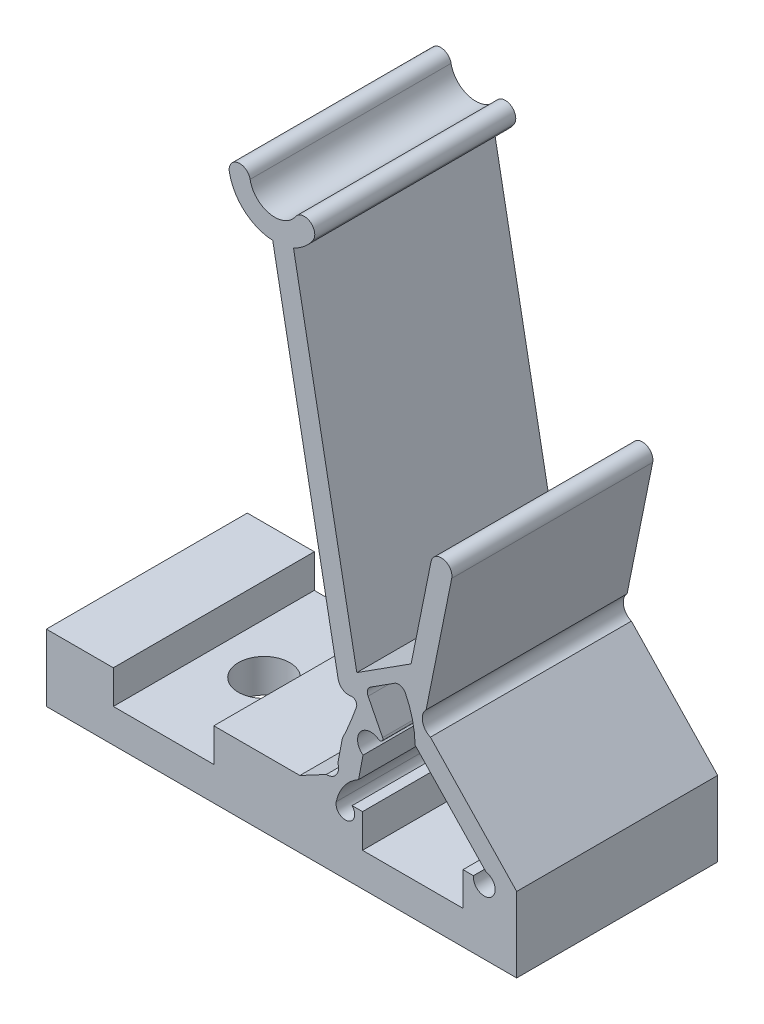
SolidWorks part; units mm, degrees
ref_plane "Front Plane" through (0, 0, 0) normal (0, 0, 1) x (1, 0, 0)
ref_plane "Top Plane" through (0, 0, 0) normal (0, 1, 0) x (1, 0, 0)
ref_plane "Right Plane" through (0, 0, 0) normal (1, 0, 0) x (0, 0, -1)
sketch "Sketch-SkeletonConfigUp" plane through (0, 0, 0) normal (0, 0, 1) x (1, 0, 0)
  line L0 (0, 0) -> (0, -50000) construction
  line L1 (0, 0) -> (7.455, 0.2734) construction
  line L2 (9.9233, 0.3639) -> (10.6101, 4.558) construction
  line L3 (10.6101, 4.558) -> (7.9471, 2.8569) construction
  line L4 (7.9471, 2.8569) -> (7.455, 0.2734) construction
  line L5 (10.6101, 4.558) -> (12.0093, 11.478) construction
  line L6 (7.9471, 2.8569) -> (4.1146, 23.199) construction
  line L7 (7.455, 0.2734) -> (9.9233, 0.3639) construction
  line L8 (-989.4051, -36.2798) -> (9.9233, 0.3639) construction
  dimension "D2" = 7.46
  dimension "D3" = 2.47
  dimension "D4" = 4.25
  dimension "D5" = 78.6
  dimension "D6" = 3.16
  dimension "D7" = 7.06
  dimension "D8" = 20.7
  dimension "D9" = 2.63
  dimension "D10" = 46
  dimension "D11" = 111.9
  dimension "D12" = 92.1
sketch "Sketch-SkeletonConfigDown" plane through (0, 0, 0) normal (0, 0, 1) x (1, 0, 0)
  line L0 (0, 0) -> (0, -50000) construction
  line L1 (0, 0) -> (7.455, 0.2734) construction
  line L2 (9.9233, 0.3639) -> (10.6101, 4.558) construction
  line L3 (10.6101, 4.558) -> (9.7761, 1.5101) construction
  line L4 (9.7761, 1.5101) -> (7.455, 0.2734) construction
  line L5 (10.6101, 4.558) -> (7.0062, 10.6288) construction
  line L6 (9.7761, 1.5101) -> (-6.7111, 14.0265) construction
  line L7 (7.455, 0.2734) -> (9.9233, 0.3639) construction
  line L8 (-993.745, -36.439) -> (9.9233, 0.3639) construction
  dimension "D2" = 7.46
  dimension "D3" = 2.47
  dimension "D4" = 4.25
  dimension "D5" = 78.6
  dimension "D6" = 3.16
  dimension "D7" = 7.06
  dimension "D8" = 20.7
  dimension "D9" = 2.63
  dimension "D10" = 46
  dimension "D11" = 111.9
  dimension "D1" = 92.1
sketch "Sketch-ConfigDown" plane through (0, 0, 0) normal (0, 0, 1) x (1, 0, 0)
  line L3 (7.2122, -0.2359) -> (5.3047, -0.3058) construction
  line L4 (9.7761, 1.5101) -> (-6.7111, 14.0265) construction
  line L6 (-200859.4238, -7365.1807) -> (9.9233, 0.3639) construction
  line L7 (7.2122, -0.2359) -> (15.5786, 0.0709) construction
  line L9 (7.455, 0.2734) -> (9.9233, 0.3639) construction
  line L10 (10.9008, 0.9001) -> (10.9374, -0.0993) construction
  line L15 (9.3493, 0.7161) -> (8.352, 0.1848)
  line L18 (8.512, 1.4031) -> (8.9823, 0.5206) construction
  line L19 (6.5762, 10.3736) -> (9.0074, 6.2784)
  line L20 (-5.3148, 12.3387) -> (8.4132, 1.917)
  line L21 (8.2015, 3.3332) -> (-4.7101, 13.1352)
  line L22 (9.7761, 1.5101) -> (7.455, 0.2734) construction
  line L23 (2.9291, 6.0802) -> (3.5338, 6.8767) construction
  line L26 (10.6101, 4.558) -> (14.4503, 0.5299) construction
  line L27 (10.2553, 5.1557) -> (9.3507, 1.85) construction
  line L28 (11.0112, 4.862) -> (15.5786, 0.0709) construction
  line L29 (14.5562, -0.3058) -> (10.7658, 3.6702) construction
  line L30 (12.9938, 1.3331) -> (13.7176, 2.0231) construction
  line L34 (5.3047, -0.3058) -> (5.3047, -3.4808) construction
  line L36 (5.3047, -3.4808) -> (15.5786, -3.4808)
  line L37 (15.5786, -3.4808) -> (15.5786, 0.0709)
  line L38 (-8.0357, 12.2817) -> (-6.0162, 14.9419) construction
  line L39 (10.6101, 4.558) -> (9.7761, 1.5101) construction
  line L40 (9.7556, 3.3297) -> (10.7202, 3.0657) construction
  line L42 (7.4361, 10.8841) -> (10.4021, 5.8879)
  line L43 (8.1032, 7.8014) -> (8.9631, 8.3119) construction
  line L44 (10.6101, 4.558) -> (7.0062, 10.6288) construction
  line L45 (7.7789, -0.3058) -> (5.3047, -0.3058) construction
  line L46 (14.5562, -0.3058) -> (15.5786, -0.3058) construction
  line L47 (13.528, -0.3058) -> (7.7789, -0.3058)
  line L48 (9.0074, 6.2784) -> (8.2015, 3.3332)
  line L49 (15.5786, 0.0709) -> (15.28, 0.3842)
  line L50 (10.7658, 3.6702) -> (9.7307, 4.7558) construction
  line L51 (15.28, 0.3842) -> (14.5562, -0.3058) construction
  line L52 (14.5815, 0.7545) -> (14.7625, 0.927) construction
  line L53 (13.5212, 0.7799) -> (14.2449, 1.4699) construction
  line L54 (11.0112, 4.862) -> (10.4545, 5.4459) construction
  line L55 (10.7911, 4.7305) -> (10.972, 4.903) construction
  line L56 (9.7307, 4.7558) -> (10.4545, 5.4459) construction
  line L57 (10.7658, 3.6702) -> (11.4896, 4.3602) construction
  line L58 (10.7911, 4.7305) -> (10.4292, 4.3855) construction
  line L59 (11.4896, 4.3602) -> (14.2449, 1.4699)
  line L60 (13.5212, 0.7799) -> (10.7658, 3.6702)
  line L61 (10.4545, 5.4459) -> (10.4021, 5.8879)
  line L62 (7.3374, 0.494) -> (7.2199, 0.7146) construction
  line L63 (7.0282, -0.5206) -> (6.3041, -0.9064) construction
  line L64 (7.8818, 1.0673) -> (8.352, 0.1848) construction
  line L65 (6.558, 0.362) -> (7.0282, -0.5206) construction
  line L66 (6.558, 0.362) -> (5.3047, -0.3058)
  line L67 (6.558, 0.362) -> (7.8818, 1.0673) construction
  line L68 (7.3374, 0.494) -> (7.5725, 0.0527) construction
  line L69 (10.2029, 2.304) -> (10.8079, 2.6264) construction
  line L70 (10.6731, 1.4215) -> (11.1125, 1.6556) construction
  line L71 (9.6585, 1.7307) -> (9.541, 1.9513) construction
  line L72 (8.8791, 1.5987) -> (9.3493, 0.7161) construction
  line L73 (10.2029, 2.304) -> (10.6731, 1.4215) construction
  line L74 (9.6585, 1.7307) -> (9.8936, 1.2894) construction
  line L75 (7.8818, 1.0673) -> (8.8791, 1.5987)
  line L76 (8.4132, 1.917) -> (9.4143, 2.4504)
  line L77 (9.6228, 4.1445) -> (11.1323, 2.561)
  line L78 (11.1323, 2.561) -> (11.3028, 2.3822)
  line L79 (-6.7111, 14.0265) -> (-5.0362, 14.2558) construction
  line L80 (-6.7111, 14.0265) -> (-6.7111, -3.4808) construction
  line L81 (5.3047, -3.4808) -> (-6.7111, -3.4808)
  line L82 (-6.7111, -3.4808) -> (-6.7111, -0.3058)
  line L83 (-6.7111, -0.3058) -> (5.3047, -0.3058)
  line L84 (8.8791, 1.5987) -> (10.2029, 2.304) construction
  arc A2 (-7.4311, 13.0782) -> (-5.5316, 14.188) centre (-6.7111, 14.0265) ccw
  arc A3 (-4.7101, 13.1352) -> (-4.5408, 14.3236) centre (-6.7111, 14.0265) ccw
  arc A4 (-8.0357, 12.2817) -> (-7.4311, 13.0782) centre (-7.7334, 12.68) cw
  arc A5 (-4.5408, 14.3236) -> (-5.5316, 14.188) centre (-5.0362, 14.2558) ccw
  arc A6 (-8.0357, 12.2817) -> (-5.3148, 12.3387) centre (-6.7111, 14.0265) ccw
  arc A7 (6.5762, 10.3736) -> (7.4361, 10.8841) centre (7.0062, 10.6288) cw
  arc A8 (15.28, 0.3842) -> (14.2449, 1.4699) centre (15.4863, 1.6171) cw
  arc A9 (14.5562, -0.3058) -> (13.5212, 0.7799) centre (13.3149, -0.453) ccw
  arc A10 (10.4545, 5.4459) -> (11.4896, 4.3602) centre (11.6958, 5.593) ccw
  arc A11 (9.7307, 4.7558) -> (10.7658, 3.6702) centre (9.5245, 3.523) cw
  arc A12 (7.8818, 1.0673) -> (6.558, 0.362) centre (6.7496, 1.5972) cw
  arc A13 (7.0282, -0.5206) -> (8.352, 0.1848) centre (8.1603, -1.0505) cw
  arc A14 (7.0282, -0.5206) -> (7.7789, -0.3058) centre (7.4971, -0.74) ccw
  arc A15 (8.8791, 1.5987) -> (10.2029, 2.304) centre (9.0707, 2.8339) ccw
  arc A16 (9.3493, 0.7161) -> (10.6731, 1.4215) centre (10.4814, 0.1863) cw
  arc A19 (10.2029, 2.304) -> (9.4143, 2.4504) centre (9.8276, 2.4796) ccw
  arc A20 (14.5562, -0.3058) -> (13.528, -0.3058) centre (14.0421, -0.3668) cw
  arc A21 (9.7307, 4.7558) -> (9.6228, 4.1445) centre (9.6795, 4.4497) ccw
  arc A22 (10.6731, 1.4215) -> (11.3028, 2.3822) centre (10.7698, 2.0448) ccw
  point P24 (8.7471, 0.9618)
  point P28 (10.9191, 0.4004)
  point P30 (8.5332, 8.0566)
  point P43 (10.2379, 3.1977)
  point P47 (14.5815, 0.7545)
  point P51 (3.2315, 6.4785)
  point P61 (13.3557, 1.6781)
  dimension "D3" = 2.3812
  dimension "D4" = 4.3812
  dimension "D1" = 1
  dimension "D8" = 1.5
  dimension "D12" = 1.5
  dimension "D6" = 7
  dimension "D2" = 3.175
  dimension "D7" = 1.5
  dimension "D9" = 1.5
  dimension "D10" = 0.25
  dimension "D11" = 1.5
  dimension "D13" = 0.5
  dimension "D14" = 0.5
  dimension "D15" = 45
sketch "Sketch-ConfigUp" plane through (0, 0, 0) normal (0, 0, 1) x (1, 0, 0)
  line L1 (7.3156, 2.2137) -> (7.1042, 1.1037)
  line L2 (8.0635, 0.796) -> (13.3219, 0.9888) construction
  line L3 (10.1988, -0.1264) -> (6.8464, -0.2493) construction
  line L4 (7.9471, 2.8569) -> (7.455, 0.2734) construction
  line L5 (11.5192, 11.5771) -> (10.5754, 6.909)
  line L6 (7.455, 0.2734) -> (9.9233, 0.3639) construction
  line L7 (10.1988, -0.1264) -> (15.5786, 0.0709) construction
  line L9 (10.6101, 4.558) -> (7.9471, 2.8569) construction
  line L10 (8.9451, 0.8283) -> (8.9817, -0.171) construction
  line L11 (7.2099, 1.6587) -> (8.1922, 1.4716) construction
  line L12 (8.7452, 3.96) -> (9.2835, 3.1173) construction
  line L15 (9.9233, 0.3639) -> (10.6101, 4.558) construction
  line L16 (9.7754, 2.5547) -> (10.7623, 2.3931) construction
  line L17 (12.4994, 11.3789) -> (11.2863, 5.379)
  line L18 (10.6101, 4.558) -> (12.0093, 11.478) construction
  line L19 (10.5058, 6.5648) -> (11.486, 6.3666) construction
  line L20 (4.0182, 21.0106) -> (7.1163, 4.5661)
  line L21 (8.0021, 5.2653) -> (5.0009, 21.1957)
  line L22 (7.9471, 2.8569) -> (4.1146, 23.199) construction
  line L23 (6.0985, 9.9681) -> (7.0813, 10.1533) construction
  line L24 (8.3015, 3.6766) -> (10.1621, 4.8651) construction
  line L26 (10.6101, 4.558) -> (14.4503, 0.5299) construction
  line L27 (-200855.0838, -7365.0216) -> (9.9233, 0.3639) construction
  line L30 (10.7658, 3.6702) -> (11.4896, 4.3602) construction
  line L34 (6.8464, -0.2493) -> (6.8464, -3.4808) construction
  line L38 (1.9619, 22.7935) -> (4.1146, 23.199) construction
  line L39 (4.1146, 23.199) -> (5.9236, 21.9636) construction
  line L40 (13.528, -0.3058) -> (7.7789, -0.3058) construction
  line L41 (13.528, -0.3058) -> (7.7789, -0.3058)
  line L42 (11.2489, 5.194) -> (10.7354, 2.6543) construction
  line L43 (10.1621, 4.8651) -> (9.715, 2.6538) construction
  line L44 (6.8464, -0.2493) -> (5.1916, -0.31) construction
  line L45 (8.0635, 0.796) -> (8.0865, 0.9166) construction
  line L46 (8.0635, 0.796) -> (7.8058, -0.5569) construction
  line L47 (7.2094, 0.3201) -> (6.9638, 0.3669) construction
  line L48 (7.2094, 0.3201) -> (7.7006, 0.2266) construction
  line L49 (6.8235, -0.3698) -> (7.8058, -0.5569) construction
  line L50 (7.4382, 2.8574) -> (7.5963, 3.6872) construction
  line L51 (8.3979, 2.5516) -> (8.5786, 3.5001) construction
  line L52 (7.3156, 2.2137) -> (8.2979, 2.0266) construction
  line L53 (7.5963, 3.6872) -> (8.5786, 3.5001) construction
  line L54 (7.7015, 2.9037) -> (8.1927, 2.8101) construction
  line L55 (7.7015, 2.9037) -> (7.4559, 2.9505) construction
  line L56 (8.1564, 2.8991) -> (7.6708, 3.0185) construction
  line L57 (7.1163, 4.5661) -> (7.4382, 2.8574) construction
  line L58 (11.2863, 5.379) -> (10.3061, 5.5772) construction
  line L59 (7.4382, 2.8574) -> (7.3156, 2.2137) construction
  line L60 (7.8068, 2.1202) -> (8.6839, 3.337) construction
  line L61 (8.2979, 2.0266) -> (8.0865, 0.9166)
  line L62 (7.1042, 1.1037) -> (8.0865, 0.9166) construction
  line L69 (10.8552, 4.5085) -> (11.1002, 4.4589) construction
  line L70 (7.7789, -0.3058) -> (5.3047, -0.3058) construction
  line L71 (7.7789, -0.3058) -> (5.3047, -0.3058) construction
  line L73 (7.1042, 1.1037) -> (6.8464, -0.2493) construction
  line L74 (10.2687, 5.3922) -> (11.2489, 5.194) construction
  line L75 (9.9714, 3.922) -> (10.9516, 3.7238) construction
  line L76 (10.8552, 4.5085) -> (10.3651, 4.6076) construction
  line L77 (8.3979, 2.5516) -> (8.2979, 2.0266) construction
  line L78 (9.5833, 3.3088) -> (8.3979, 2.5516) construction
  line L79 (8.0021, 5.2653) -> (10.5754, 6.909)
  line L80 (8.0021, 5.2653) -> (8.3015, 3.6766) construction
  line L81 (10.5058, 6.5648) -> (10.1621, 4.8651) construction
  line L82 (10.5058, 6.5648) -> (10.5754, 6.909) construction
  line L83 (11.4896, 4.3602) -> (10.7658, 3.6702) construction
  line L84 (11.1158, 4.8153) -> (10.6255, 4.7174) construction
  line L106 (6.558, 0.362) -> (5.3047, -0.3058)
  line L107 (5.3047, -0.3058) -> (-6.7111, -0.3058)
  line L108 (-6.7111, -0.3058) -> (-6.7111, -3.4808)
  line L109 (-6.7111, -3.4808) -> (15.5786, -3.4808)
  line L110 (15.5786, -3.4808) -> (15.5786, 0.0709)
  line L112 (15.5786, 0.0709) -> (11.4896, 4.3602)
  line L114 (11.1277, 4.0152) -> (10.7962, 5.4781) construction
  line L115 (9.5833, 3.3088) -> (10.5323, 3.915) construction
  line L116 (13.3219, 0.9888) -> (10.7658, 3.6702)
  line L117 (10.7658, 3.6702) -> (10.5323, 3.915) construction
  line L118 (10.6101, 4.558) -> (7.9471, 2.8569) construction
  line L119 (8.6839, 3.337) -> (9.4161, 2.8092) construction
  line L120 (8.6839, 3.337) -> (7.8068, 3.9692) construction
  line L121 (9.0288, 3.0406) -> (8.2979, 2.0266) construction
  line L123 (9.7888, 5.7212) -> (8.6571, 4.9983)
  line L124 (8.5388, 4.5661) -> (9.2253, 3.2085)
  line L126 (13.3219, 0.9888) -> (14.1275, 0.1438)
  line L127 (11.2489, 5.194) -> (11.2863, 5.379) construction
  arc A0 (11.5192, 11.5771) -> (12.4994, 11.3789) centre (12.0093, 11.478) cw
  arc A2 (2.9446, 22.9786) -> (5.0978, 22.5276) centre (4.1146, 23.199) ccw
  arc A3 (5.0009, 21.1957) -> (5.9236, 21.9636) centre (4.1146, 23.199) ccw
  arc A4 (1.9619, 22.7935) -> (2.9446, 22.9786) centre (2.4533, 22.886) cw
  arc A5 (5.9236, 21.9636) -> (5.0978, 22.5276) centre (5.5107, 22.2456) ccw
  arc A6 (1.9619, 22.7935) -> (4.0182, 21.0106) centre (4.1146, 23.199) ccw
  arc A7 (13.528, -0.3058) -> (14.5562, -0.3058) centre (14.0421, -0.3668) ccw construction
  arc A8 (13.528, -0.3058) -> (14.1275, 0.1438) centre (14.0421, -0.3668) ccw
  arc A9 (7.1042, 1.1037) -> (6.8235, -0.3698) centre (5.9815, 0.554) cw construction
  arc A10 (7.8058, -0.5569) -> (8.0865, 0.9166) centre (8.9285, -0.0073) cw construction
  arc A11 (7.3156, 2.2137) -> (7.5963, 3.6872) centre (6.4736, 3.1376) ccw construction
  arc A12 (8.2979, 2.0266) -> (8.5786, 3.5001) centre (9.4206, 2.5762) cw construction
  arc A13 (11.2489, 5.194) -> (10.9516, 3.7238) centre (12.0804, 4.2607) ccw construction
  arc A14 (10.2687, 5.3922) -> (9.9714, 3.922) centre (9.1399, 4.8553) cw construction
  arc A15 (8.0865, 0.9166) -> (7.0282, -0.5206) centre (9.1391, -0.9668) ccw
  arc A16 (7.1042, 1.1037) -> (6.558, 0.362) centre (6.5823, 0.916) cw
  arc A17 (7.0282, -0.5206) -> (7.7789, -0.3058) centre (7.4604, -0.612) ccw
  arc A18 (11.4896, 4.3602) -> (11.2863, 5.379) centre (11.7287, 4.9376) cw
  arc A19 (8.2979, 2.0266) -> (9.0288, 3.0406) centre (8.6634, 2.5336) cw
  arc A21 (7.3156, 2.2137) -> (7.9864, 3.8397) centre (-8.9784, 9.887) ccw
  arc A22 (7.9864, 3.8397) -> (7.7104, 4.1617) centre (7.7563, 3.9218) ccw
  arc A23 (10.7658, 3.6702) -> (10.3061, 5.5772) centre (6.3229, 3.6081) ccw
  arc A24 (7.7104, 4.1617) -> (7.1163, 4.5661) centre (7.615, 4.66) cw
  arc A25 (9.0288, 3.0406) -> (9.2253, 3.2085) centre (9.1066, 3.1485) ccw
  arc A27 (10.3061, 5.5772) -> (9.7888, 5.7212) centre (9.9829, 5.4174) ccw
  arc A39 (8.6571, 4.9983) -> (8.5388, 4.5661) centre (8.8369, 4.7168) ccw
  point P25 (9.0144, 3.5387)
  point P27 (7.701, 1.5651)
  point P28 (8.9634, 0.3287)
  point P36 (10.2689, 2.4739)
  point P38 (10.9959, 6.4657)
  point P51 (6.5899, 10.0607)
  point P61 (11.1277, 4.0152)
  dimension "D3" = 2.3812
  dimension "D4" = 4.3812
  dimension "D13" = 0.625
  dimension "D17" = 0.625
  dimension "D1" = 1
  dimension "D5" = 7
  dimension "D10" = 1.5
  dimension "D11" = 0.25
  dimension "D8" = 1.5
  dimension "D9" = 0.25
  dimension "D6" = 1.5
  dimension "D7" = 0.25
  dimension "D12" = 1.5
  dimension "D15" = 0.5
  dimension "D16" = 1.5
  dimension "D18" = 0.5
  dimension "D19" = 25
  dimension "D20" = 1.5
  dimension "D14" = 45
extrude "Boss-ConfigUp" add sketch "Sketch-ConfigUp" along normal blind 9.525
sketch "Sketch2" plane through (0.0043, -0.3058, 0) normal (0, -1, 0) x (-1, 0, 0)
  line L1 (-13.0304, 0) -> (-8.2679, 0)
  line L2 (-13.0304, 0) -> (-13.0304, -9.525)
  line L3 (-13.0304, -9.525) -> (-8.2679, -9.525)
  line L4 (-8.2679, 0) -> (-8.2679, -9.525)
  line L5 (-13.5237, 0) -> (-13.0304, 0) construction
  line L7 (-8.2679, 0) -> (-7.7746, 0) construction
  line L10 (-15.5743, -4.7625) -> (6.7155, -4.7625) construction
  line L12 (-13.0304, 0) -> (-8.2679, -9.525) construction
  line L17 (-13.0304, -9.525) -> (-8.2679, 0) construction
  line L18 (6.7155, 0) -> (-15.5743, 0) construction
  line L19 (6.7155, -9.525) -> (6.7155, 0) construction
  line L20 (3.5405, -9.525) -> (3.5405, 0)
  line L21 (3.5405, -9.525) -> (-1.222, -9.525)
  line L22 (3.5405, 0) -> (-1.222, 0)
  line L23 (-1.222, -9.525) -> (-1.222, 0)
  line L24 (3.5405, -9.525) -> (-1.222, 0) construction
  line L25 (3.5405, 0) -> (-1.222, -9.525) construction
  line L26 (6.7155, -9.525) -> (-15.5743, -9.525) construction
  line L27 (-15.5743, -9.525) -> (-15.5743, 0) construction
  point P4 (-10.6492, -4.7625)
  point P26 (1.1592, -4.7625)
  dimension "D1" = 4.7625
  dimension "D2" = 3.175
extrude "Cut-NutSlot" cut sketch "Sketch2" along normal blind 1.5875
hole_wizard "#2 Clearance Hole1" positions "Sketch4" profile "Sketch3" hole size "#2" standard "ANSI Inch" end condition up to next
sketch "Sketch4" plane through (0, -3.4808, 0) normal (0, -1, 0) x (-1, 0, 0)
  line L16 (-13.0347, 0) -> (-8.2722, -9.525) construction
  point P40 (-10.6535, -4.7625)
  point P44 (1.1549, -4.7625)
sketch "Sketch3" plane through (10.6535, -3.4808, 4.7625) normal (1, 0, 0) x (0, 0, -1)
  line L0 (0, 0) -> (0, 1.5875)
  line L1 (0, 1.5875) -> (1.2192, 1.5875)
  line L2 (1.2192, 1.5875) -> (1.2192, 0)
  line L5 (1.2192, 0) -> (0, 0)
  line L11 (0, -6.35) -> (0, 107.95) construction
  dimension "Thru Hole Dia." = 2.4384
  dimension "Thru Hole Depth" = 1.5875
ref_plane "Plane-Midplane" through (0, 0, 4.7625) normal (0, 0, -1) x (-1, 0, 0)
equation "\"axle-diameter\"=2"
equation "\"switch-thickness\"=12"
equation "\"base-width\"=4.0"
equation "\"axle-bushing-radius\"=3"
equation "\"clearance\"= 0.25"
equation "\"arm-width\"=1.0"
equation "\"min-diameter\"=70"
equation "\"alpha\"=92.1"
equation "\"beta\"=26.0"
equation "\"gamma\"=78.6"
equation "\"delta\"=111.9"
equation "\"epsilon\"=46.0"
equation "\"eta\"=-228.1"
equation "\"l_AB\"=2.47"
equation "\"l_AC\"=2.63"
equation "\"l_BD\"=4.25"
equation "\"l_CD\"=3.16"
equation "\"l_CE\"=20.70"
equation "\"l_DF\"=7.06"
equation "\"l_OA\"=7.46"
equation "\"D2@Sketch-SkeletonConfigUp\" = \"l_OA\""
equation "\"D3@Sketch-SkeletonConfigUp\" = \"l_AB\""
equation "\"D4@Sketch-SkeletonConfigUp\" = \"l_BD\""
equation "\"D5@Sketch-SkeletonConfigUp\" = \"gamma\""
equation "\"D6@Sketch-SkeletonConfigUp\" = \"l_CD\""
equation "\"D7@Sketch-SkeletonConfigUp\" = \"l_DF\""
equation "\"D8@Sketch-SkeletonConfigUp\" = \"l_CE\""
equation "\"D9@Sketch-SkeletonConfigUp\" = \"l_AC\""
equation "\"D_groove\"=2.3812"
equation "\"D3@Sketch-ConfigUp\" = \"D_groove\""
equation "\"D4@Sketch-ConfigUp\" = \"D_groove\" + 2 * \"arm-width\""
equation "\"D7@Sketch-SkeletonConfigDown\" = \"l_DF\""
equation "\"D6@Sketch-SkeletonConfigDown\" = \"l_CD\""
equation "\"D2@Sketch-SkeletonConfigDown\" = \"l_OA\""
equation "\"D3@Sketch-SkeletonConfigDown\" = \"l_AB\""
equation "\"D9@Sketch-SkeletonConfigDown\" = \"l_AC\""
equation "\"D8@Sketch-SkeletonConfigDown\" = \"l_CE\""
equation "\"D5@Sketch-SkeletonConfigDown\" = \"gamma\""
equation "\"D4@Sketch-SkeletonConfigDown\" = \"l_BD\""
equation "\"D1@Sketch-SkeletonConfigDown\" = \"alpha\""
equation "\"D5@Sketch-ConfigDown\" = \"arm-width\""
equation "\"hinge_length\"=1.5"
equation "\"hinge_depth\"=0.25"
equation "\"D9@Sketch-ConfigDown\" = \"hinge_length\""
equation "\"D10@Sketch-ConfigDown\" = \"hinge_depth\""
equation "\"D8@Sketch-ConfigDown\" = \"hinge_length\""
equation "\"D11@Sketch-ConfigDown\" = \"hinge_length\""
equation "\"D12@Sketch-ConfigDown\" = \"hinge_length\""
equation "\"D10@Sketch-ConfigUp\" = \"hinge_length\""
equation "\"D11@Sketch-ConfigUp\" = \"hinge_depth\""
equation "\"D8@Sketch-ConfigUp\" = \"hinge_length\""
equation "\"D9@Sketch-ConfigUp\" = \"hinge_depth\""
equation "\"D6@Sketch-ConfigUp\" = \"hinge_length\""
equation "\"D7@Sketch-ConfigUp\" = \"hinge_depth\""
equation "\"D10@Sketch-SkeletonConfigUp\"=\"epsilon\""
equation "\"D11@Sketch-SkeletonConfigUp\"=\"delta\""
equation "\"D12@Sketch-SkeletonConfigUp\"=\"alpha\""
equation "\"D11@Sketch-SkeletonConfigDown\"=\"delta\""
equation "\"D10@Sketch-SkeletonConfigDown\"=\"epsilon\""
equation "\"D15@Sketch-ConfigUp\"=2*\"hinge_depth\""
equation "\"D16@Sketch-ConfigUp\"=\"hinge_length\""
equation "\"D18@Sketch-ConfigUp\"=2*\"hinge_depth\""
equation "\"D20@Sketch-ConfigUp\"=\"hinge_length\""
